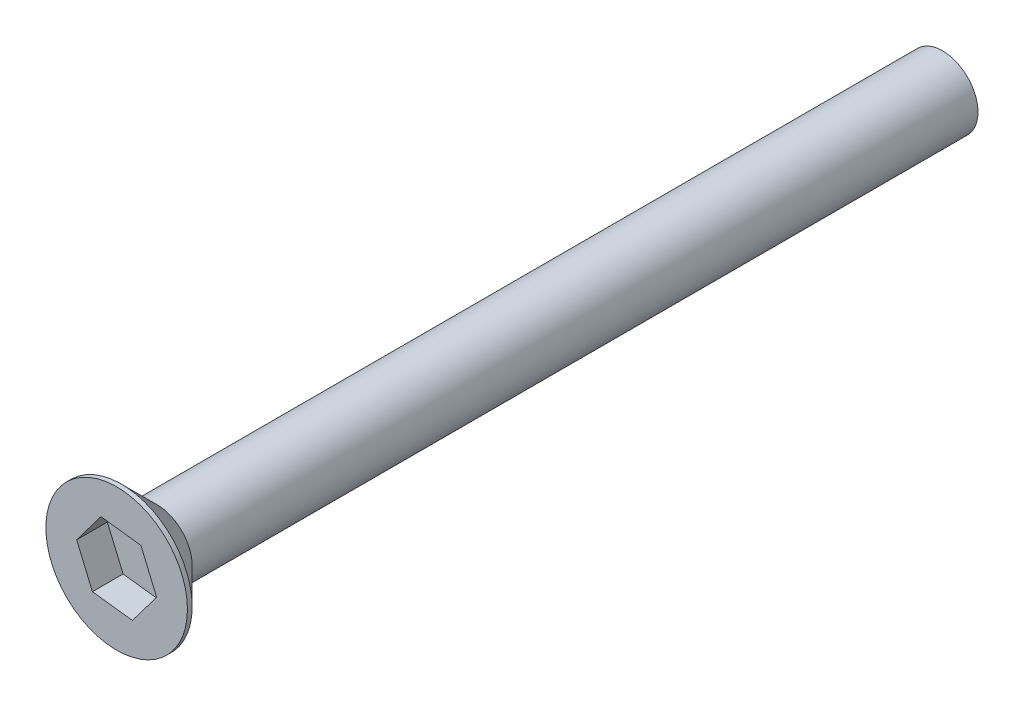
SolidWorks part; units mm, degrees
ref_plane "Front Plane" through (0, 0, 0) normal (0, 0, 1) x (1, 0, 0)
ref_plane "Top Plane" through (0, 0, 0) normal (0, 1, 0) x (1, 0, 0)
ref_plane "Right Plane" through (0, 0, 0) normal (1, 0, 0) x (0, 0, -1)
sketch "Sketch1" plane through (0, 0, 0) normal (0, 0, 1) x (1, 0, 0)
  circle A0 centre (0, 0) radius 1.5
  dimension "D1" = 3
extrude "Boss-Extrude1" add sketch "Sketch1" along normal blind 33.3
sketch "Sketch2" plane through (0, 0, 33.3) normal (0, 0, 1) x (1, 0, 0)
  circle A0 centre (0, 0) radius 3
  dimension "D1" = 6
extrude "Boss-Extrude2" add sketch "Sketch2" along normal blind 1.7
chamfer "Chamfer1" distance 1.5 angle 45 1 edges at (3, 0, 33.3)
sketch "Sketch7" plane through (0, 0, 35) normal (0, 0, 1) x (1, 0, 0)
  line L1 (0.6672, -1.5714) -> (1.6945, -0.2079)
  line L2 (1.6945, -0.2079) -> (1.0273, 1.3635)
  line L3 (1.0273, 1.3635) -> (-0.6672, 1.5714)
  line L4 (-0.6672, 1.5714) -> (-1.6945, 0.2079)
  line L5 (-1.6945, 0.2079) -> (-1.0273, -1.3635)
  line L6 (-1.0273, -1.3635) -> (0.6672, -1.5714)
  circle A0 centre (0, 0) radius 1.4785 construction
extrude "Cut-Extrude1" cut sketch "Sketch7" against normal blind 1.3
